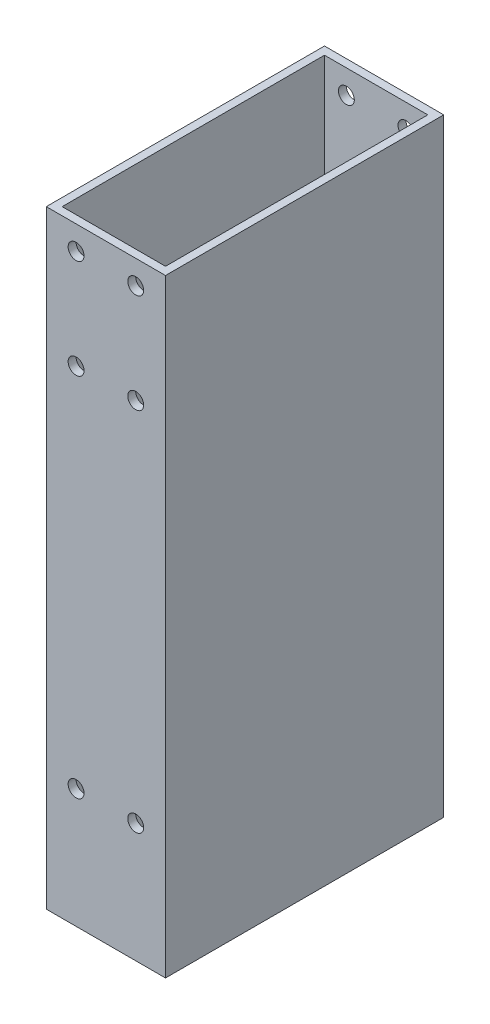
SolidWorks part; units mm, degrees
ref_plane "前视基准面" through (0, 0, 0) normal (0, 0, 1) x (1, 0, 0)
ref_plane "上视基准面" through (0, 0, 0) normal (0, 1, 0) x (1, 0, 0)
ref_plane "右视基准面" through (0, 0, 0) normal (1, 0, 0) x (0, 0, -1)
other "Configuration Table"
sketch "草图1" plane through (0, 0, 0) normal (0, 0, 1) x (1, 0, 0)
  line L1 (15, -383.07) -> (-15, -383.07)
  line L2 (15, -383.07) -> (15, 383.07)
  line L3 (15, 383.07) -> (-15, 383.07)
  line L4 (-15, -383.07) -> (-15, 383.07)
  line L5 (15, -383.07) -> (-15, 383.07) construction
  line L6 (15, 383.07) -> (-15, -383.07) construction
  circle A0 centre (-7.5, 377.0748) radius 2
  circle A1 centre (7.5, 377.0748) radius 2
  circle A2 centre (-7.5, 352.0748) radius 2
  circle A3 centre (7.5, 352.0748) radius 2
  circle A4 centre (7.4999, 260) radius 2 construction
  circle A5 centre (-7.5001, 260) radius 2 construction
  circle A6 centre (7.4999, 260) radius 2
  circle A7 centre (-7.5001, 260) radius 2
  point P0 (0, 0)
  point P8 (0, 0)
  dimension "D1" = 30
  dimension "D2" = 766.14
extrude "凸台-拉伸2" add sketch "草图1" along normal blind 70
sketch "草图2" plane through (0, -383.07, 0) normal (0, -1, 0) x (1, 0, 0)
  line L0 (-15, 70) -> (-15, 0) construction
  line L1 (-13, 68) -> (13, 68)
  line L2 (-13, 68) -> (-13, 2)
  line L3 (-13, 2) -> (13, 2)
  line L4 (13, 68) -> (13, 2)
  line L5 (-13, 68) -> (13, 2) construction
  line L6 (-13, 2) -> (13, 68) construction
  line L7 (-15, 70) -> (15, 70) construction
  line L8 (15, 70) -> (15, 0) construction
  line L9 (-15, 0) -> (15, 0) construction
  point P0 (0, 35)
  dimension "D1" = 2
  dimension "D2" = 2
  dimension "D3" = 2
  dimension "D4" = 2
extrude "切除-拉伸3" cut sketch "草图2" against normal through all contours L2 L1 L4 L3
sketch "草图3" plane through (0, 0, 70) normal (0, 0, 1) x (1, 0, 0)
  line L0 (-15, 230) -> (15, 230)
  line L1 (-15, 383.07) -> (-15, -383.07) construction
  line L2 (15, -383.07) -> (15, 383.07) construction
  line L3 (15, 383.07) -> (-15, 383.07) construction
  line L4 (-15, 230) -> (-15, -394.9368)
  line L5 (-15, -394.9368) -> (15, -394.9368)
  line L6 (15, -394.9368) -> (15, 230)
  dimension "D1" = 153.07
extrude "切除-拉伸4" cut sketch "草图3" against normal through all
